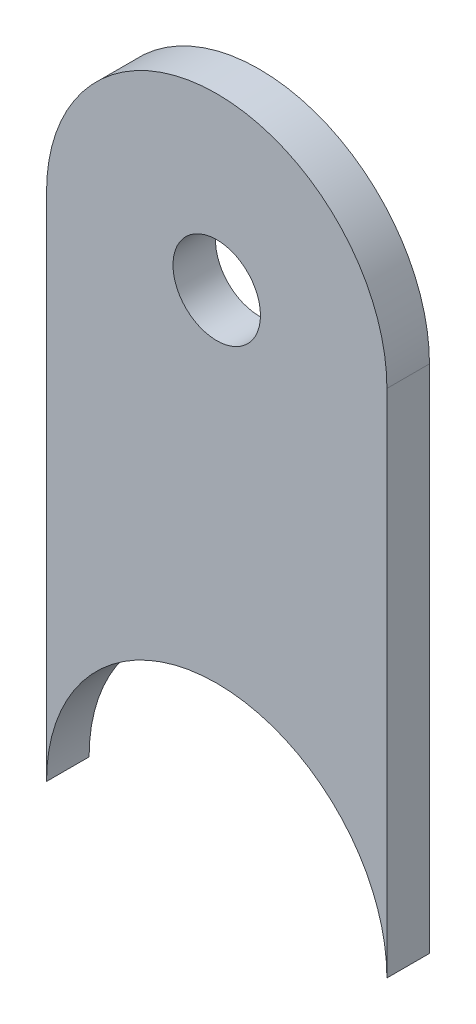
SolidWorks part; units mm, degrees
ref_plane "Front Plane" through (0, 0, 0) normal (0, 0, 1) x (1, 0, 0)
ref_plane "Top Plane" through (0, 0, 0) normal (0, 1, 0) x (1, 0, 0)
ref_plane "Right Plane" through (0, 0, 0) normal (1, 0, 0) x (0, 0, -1)
sketch "Sketch1" plane through (0, 0, 0) normal (0, 0, 1) x (1, 0, 0)
  line L0 (0, 0) -> (0, 38.1)
  line L1 (0, 0) -> (25.4, 0)
  line L2 (25.4, 0) -> (25.4, 38.1)
  line L3 (12.7, 34.8361) -> (12.7, 0)
  arc A0 (0, 38.1) -> (25.4, 38.1) centre (12.7, 38.1) cw
  circle A1 centre (12.7, 38.1) radius 3.2639
  circle A2 centre (12.7, 0) radius 12.7
  point P7 (12.7, 0)
  dimension "D1" = 6.5278
  dimension "D2" = 25.4
  dimension "D3" = 38.1
extrude "Boss-Extrude1" add sketch "Sketch1" along normal blind 3.175 contours A2 L2 A0 L0 A1 region at (0.568, 19.05, 0)
